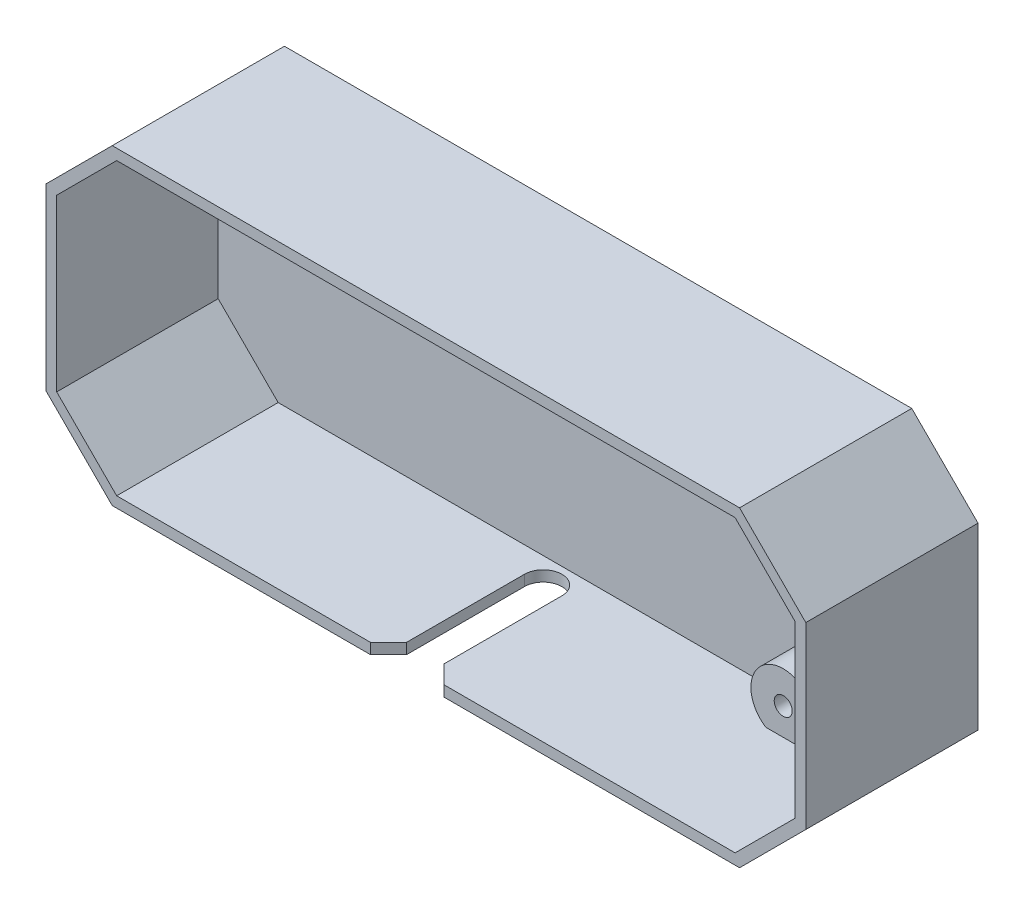
SolidWorks part; units mm, degrees
ref_plane "Front Plane" through (0, 0, 0) normal (0, 0, 1) x (1, 0, 0)
ref_plane "Top Plane" through (0, 0, 0) normal (0, 1, 0) x (1, 0, 0)
ref_plane "Right Plane" through (0, 0, 0) normal (1, 0, 0) x (0, 0, -1)
sketch "Sketch1" plane through (0, 0, 0) normal (0, 0, 1) x (1, 0, 0)
  line L1 (-28.3844, -11.6458) -> (28.3844, -11.6458)
  line L2 (-28.3844, -11.6458) -> (-28.3844, 11.6458)
  line L3 (-28.3844, 11.6458) -> (28.3844, 11.6458)
  line L4 (28.3844, -11.6458) -> (28.3844, 11.6458)
  line L5 (-28.3844, -11.6458) -> (28.3844, 11.6458) construction
  line L6 (-28.3844, 11.6458) -> (28.3844, -11.6458) construction
  point P0 (0, 0)
  dimension "D1" = 56.7688
  dimension "D2" = 23.2916
extrude "Boss-Extrude1" add sketch "Sketch1" along normal blind 0.8
sketch "Sketch2" plane through (0, 0, 0.8) normal (0, 0, 1) x (1, 0, 0)
  line L0 (-28.3844, -6.6961) -> (-23.4347, -11.6458)
  line L1 (-28.3844, 11.6458) -> (-28.3844, -11.6458) construction
  line L2 (-28.3844, 6.6961) -> (-23.4347, 11.6458)
  line L3 (28.3844, 11.6458) -> (-28.3844, 11.6458) construction
  line L4 (-23.4347, 11.6458) -> (-28.3844, 11.6458)
  line L5 (-28.3844, 11.6458) -> (-28.3844, 6.6961)
  line L6 (-28.3844, -11.6458) -> (28.3844, -11.6458) construction
  line L7 (-23.4347, -11.6458) -> (-28.3844, -11.6458)
  line L8 (-28.3844, -11.6458) -> (-28.3844, -6.6961)
  line L9 (23.4347, -11.6458) -> (28.3844, -6.6961)
  line L10 (28.3844, -11.6458) -> (28.3844, 11.6458) construction
  line L11 (28.3844, -6.6961) -> (28.3844, -11.6458)
  line L12 (28.3844, -11.6458) -> (23.4347, -11.6458)
  line L13 (23.4347, 11.6458) -> (28.3844, 6.6961)
  line L14 (28.3844, 6.6961) -> (28.3844, 11.6458)
  line L15 (28.3844, 11.6458) -> (23.4347, 11.6458)
  dimension "D1" = 7
  dimension "D2" = 7
  dimension "D3" = 7
  dimension "D4" = 7
  dimension "D5" = 45
  dimension "D6" = 45
  dimension "D7" = 45
  dimension "D8" = 45
extrude "Cut-Extrude1" cut sketch "Sketch2" against normal through all
sketch "Sketch3" plane through (0, 0, 0.8) normal (0, 0, 1) x (1, 0, 0)
  line L0 (23.4347, 11.6458) -> (-23.4347, 11.6458)
  line L1 (-23.4347, 11.6458) -> (-28.3844, 6.6961)
  line L2 (-28.3844, 6.6961) -> (-28.3844, -6.6961)
  line L3 (-28.3844, -6.6961) -> (-23.4347, -11.6458)
  line L4 (-23.4347, -11.6458) -> (23.4347, -11.6458)
  line L5 (23.4347, -11.6458) -> (28.3844, -6.6961)
  line L6 (28.3844, -6.6961) -> (28.3844, 6.6961)
  line L7 (28.3844, 6.6961) -> (23.4347, 11.6458)
  line L48 (-23.1033, 10.8458) -> (-27.5844, 6.3647)
  line L49 (-27.5844, 6.3647) -> (-27.5844, -6.3647)
  line L50 (-27.5844, -6.3647) -> (-23.1033, -10.8458)
  line L51 (-23.1033, -10.8458) -> (23.1033, -10.8458)
  line L52 (23.1033, -10.8458) -> (27.5844, -6.3647)
  line L53 (27.5844, -6.3647) -> (27.5844, 6.3647)
  line L54 (27.5844, 6.3647) -> (23.1033, 10.8458)
  line L55 (23.1033, 10.8458) -> (-23.1033, 10.8458)
  line L56 (-23.1033, 10.8458) -> (-27.5844, 6.3647)
  line L57 (-27.5844, 6.3647) -> (-27.5844, -6.3647)
  line L58 (-27.5844, -6.3647) -> (-23.1033, -10.8458)
  line L59 (-23.1033, -10.8458) -> (23.1033, -10.8458)
  line L60 (23.1033, -10.8458) -> (27.5844, -6.3647)
  line L61 (27.5844, -6.3647) -> (27.5844, 6.3647)
  line L62 (27.5844, 6.3647) -> (23.1033, 10.8458)
  line L63 (23.1033, 10.8458) -> (-23.1033, 10.8458)
  dimension "D1" = 0.8
  dimension "D2" = 0.8
extrude "Boss-Extrude2" add sketch "Sketch3" along normal blind 12.065
sketch "Sketch4" plane through (0, 0, 0.8) normal (0, 0, 1) x (1, 0, 0)
  line L0 (23.1033, 10.8458) -> (-23.1033, 10.8458) construction
  line L1 (-23.1033, -10.8458) -> (23.1033, -10.8458) construction
  line L2 (-27.5844, 6.3647) -> (-27.5844, -6.3647) construction
  line L3 (27.5844, -6.3647) -> (27.5844, 6.3647) construction
  circle A0 centre (-21.9964, 8.8138) radius 2.413
  circle A1 centre (17.4244, -8.8138) radius 2.413
  dimension "D1" = 4.826
  dimension "D2" = 4.826
  dimension "D3" = 2.032
  dimension "D4" = 2.032
  dimension "D5" = 10.16
  dimension "D6" = 5.588
extrude "Boss-Extrude3" add sketch "Sketch4" along normal blind 2.794
sketch "Sketch5" plane through (0, 0, 3.594) normal (0, 0, 1) x (1, 0, 0)
  circle A0 centre (-21.9964, 8.8138) radius 0.6731
  circle A1 centre (17.4244, -8.8138) radius 0.6731
  dimension "D1" = 1.3462
  dimension "D2" = 1.3462
extrude "Cut-Extrude2" cut sketch "Sketch5" against normal up to surface (2.794 mm away) up to face at (1.2932, -1.027, 0.8)
sketch "Sketch6" plane through (0, -11.6458, 0) normal (0, -1, 0) x (-1, 0, 0)
  line L0 (-1.347, -12.865) -> (4.141, -12.865)
  line L1 (23.4347, -12.865) -> (-23.4347, -12.865) construction
  line L3 (0, -11.518) -> (0, -2.705)
  line L4 (2.794, -11.518) -> (4.141, -12.865)
  line L6 (0, -11.518) -> (-1.347, -12.865)
  line L8 (2.794, -2.705) -> (2.794, -11.518)
  arc A0 (2.794, -2.705) -> (0, -2.705) centre (1.397, -2.705) ccw
  dimension "D2" = 1.397
  dimension "D1" = 45
  dimension "D3" = 2.794
  dimension "D4" = 1.905
  dimension "D5" = 1.905
  dimension "D6" = 45
  dimension "D7" = 10.16
extrude "Cut-Extrude3" cut sketch "Sketch6" against normal blind 2.794
